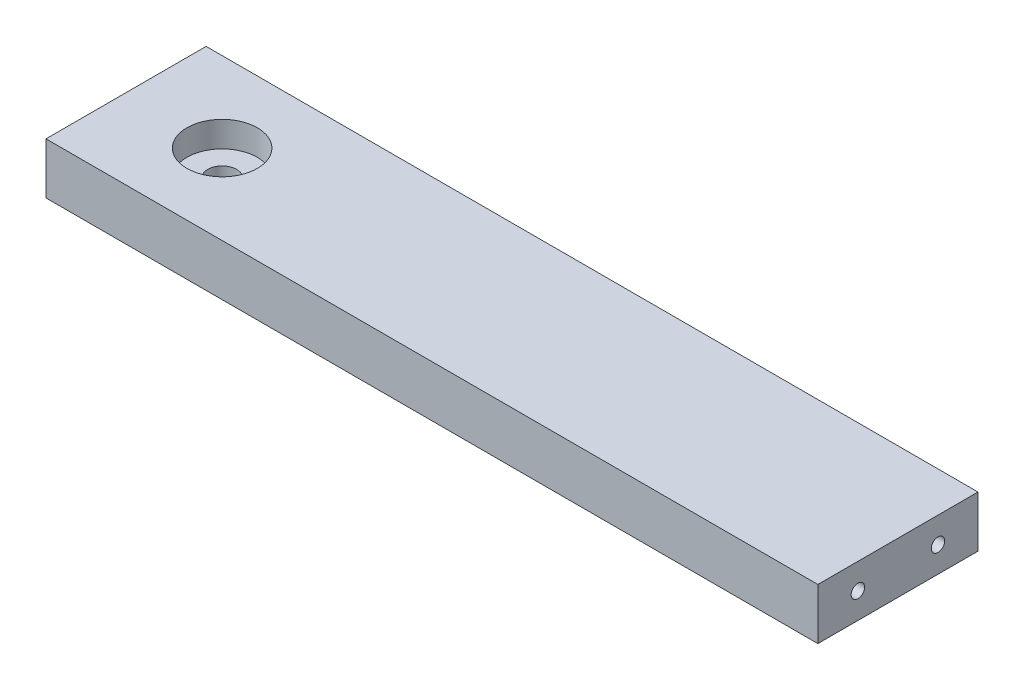
SolidWorks part; units mm, degrees
ref_plane "Front Plane" through (0, 0, 0) normal (0, 0, 1) x (1, 0, 0)
ref_plane "Top Plane" through (0, 0, 0) normal (0, 1, 0) x (1, 0, 0)
ref_plane "Right Plane" through (0, 0, 0) normal (1, 0, 0) x (0, 0, -1)
sketch "Sketch2" plane through (0, 0, 0) normal (0, 1, 0) x (1, 0, 0)
  line L1 (120.5, -25) -> (-120.5, -25)
  line L2 (120.5, -25) -> (120.5, 25)
  line L3 (120.5, 25) -> (-120.5, 25)
  line L4 (-120.5, -25) -> (-120.5, 25)
  line L5 (120.5, -25) -> (-120.5, 25) construction
  line L6 (120.5, 25) -> (-120.5, -25) construction
  point P0 (0, 0)
  dimension "D1" = 241
  dimension "D2" = 50
extrude "Boss-Extrude1" add sketch "Sketch2" along normal blind 16
sketch "Sketch3" plane through (0, 16, 0) normal (0, 1, 0) x (1, 0, 0)
  line L0 (-120.5, 25) -> (-120.5, -25) construction
  line L2 (120.5, 25) -> (-120.5, 25) construction
  circle A0 centre (-90.5, 0) radius 11
  dimension "D1" = 22
  dimension "D2" = 30
  dimension "D3" = 25
extrude "Cut-Extrude1" cut sketch "Sketch3" against normal blind 8
sketch "Sketch6" plane through (0, 8, 0) normal (0, 1, 0) x (1, 0, 0)
  circle A0 centre (-90.5, 0) radius 4.5
  dimension "D1" = 9
extrude "Cut-Extrude2" cut sketch "Sketch6" against normal through all
hole_wizard "M5 Tapped Hole4" positions "Sketch20" profile "Sketch21" tap size "M5" standard "ISO"
sketch "Sketch20" plane through (120.5, 0, 0) normal (1, 0, 0) x (0, 0, -1)
  line L0 (-25, 16) -> (25, 16) construction
  line L1 (0, 0) -> (0, 16) construction
  line L2 (-25, 0) -> (25, 0) construction
  point P0 (-12.5, 8)
  point P2 (12.5, 8)
  dimension "D1" = 25
  dimension "D2" = 8
  dimension "D3" = 12.5
sketch "Sketch21" plane through (120.5, 8, 12.5) normal (0, 1, 0) x (0, 0, -1)
  line L0 (0, 0) -> (0, 23.6618)
  line L1 (0, 23.6618) -> (2.1, 22.4)
  line L2 (2.1, 22.4) -> (2.1, 0)
  line L5 (2.1, 0) -> (0, 0)
  line L10 (0, 23.6618) -> (-2.1, 22.4) construction
  line L11 (0, -6.35) -> (0, 107.95) construction
  dimension "Tap Drill Dia." = 4.2
  dimension "Tap Drill Depth" = 22.4
  dimension "Drill Angle" = 118
